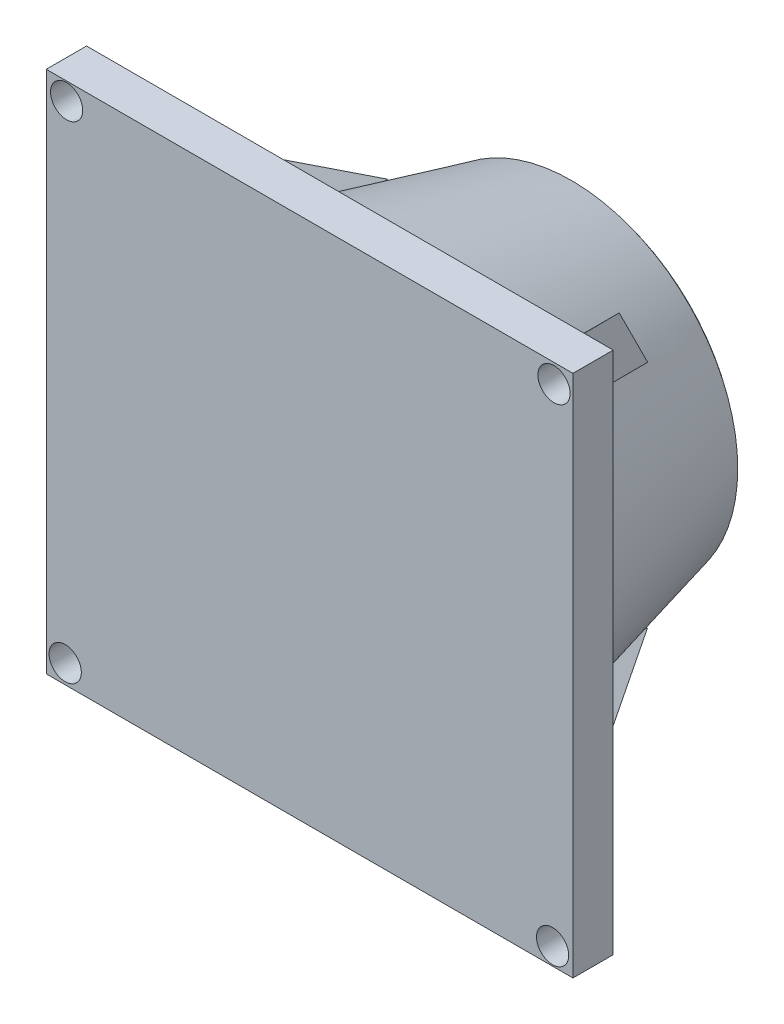
SolidWorks part; units mm, degrees
ref_plane "Piano frontale" through (0, 0, 0) normal (0, 0, 1) x (1, 0, 0)
ref_plane "Piano superiore" through (0, 0, 0) normal (0, 1, 0) x (1, 0, 0)
ref_plane "Piano destro" through (0, 0, 0) normal (1, 0, 0) x (0, 0, -1)
ref_plane "Piano5" through (0, 0, 10) normal (0, 0, 1) x (1, 0, 0)
sketch "Schizzo1" plane through (0, 0, 10) normal (0, 0, 1) x (1, 0, 0)
  arc A3 (159.4619, 183.1285) -> (159.4619, 201.9529) centre (159.4619, 192.5407) ccw
  arc A4 (159.4619, 201.9529) -> (159.4619, 183.1285) centre (159.4619, 192.5407) ccw
  arc A5 (142.3549, 173.8547) -> (142.3549, 155.0303) centre (142.3549, 164.4425) ccw
  arc A6 (142.3549, 155.0303) -> (142.3549, 173.8547) centre (142.3549, 164.4425) ccw
  arc A7 (142.3549, -155.0303) -> (142.3549, -173.8547) centre (142.3549, -164.4425) ccw
  arc A8 (142.3549, -173.8547) -> (142.3549, -155.0303) centre (142.3549, -164.4425) ccw
  arc A9 (159.4619, -183.1285) -> (159.4619, -201.9529) centre (159.4619, -192.5407) ccw
  arc A10 (159.4619, -201.9529) -> (159.4619, -183.1285) centre (159.4619, -192.5407) ccw
  arc A11 (-217.5, 9.4122) -> (-217.5, -9.4122) centre (-217.5, 0) ccw
  arc A12 (-217.5, -9.4122) -> (-217.5, 9.4122) centre (-217.5, 0) ccw
  arc A13 (-250, 9.4122) -> (-250, -9.4122) centre (-250, 0) ccw
  arc A14 (-250, -9.4122) -> (-250, 9.4122) centre (-250, 0) ccw
  circle A15 centre (0, 0) radius 400
  dimension "D1" = 800
  dimension "D2" = 0
  dimension "D3" = 217.5
  dimension "D4" = 250
  dimension "D5" = 217.5
  dimension "D6" = 250
  dimension "D7" = 217.5
  dimension "D8" = 250
extrude "Estrusione-Estrusione2" add sketch "Schizzo1" against normal blind 10
ref_plane "Piano1" through (0, 0, 560) normal (0, 0, 1) x (1, 0, 0)
sketch "Schizzo2" plane through (0, 0, 560) normal (0, 0, 1) x (1, 0, 0)
  circle A2 centre (0, 0) radius 550
  dimension "D1" = 1100
  dimension "D2" = 0
extrude "Estrusione-Estrusione3" add sketch "Schizzo2" against normal up to surface (550 mm away) draft 14 contours A2
sketch "Schizzo7" plane through (0, 0, 560) normal (0, 0, 1) x (1, 0, 0)
  line L1 (-653.7561, 650) -> (653.7561, 650)
  line L2 (-653.7561, 650) -> (-653.7561, -650)
  line L3 (-653.7561, -650) -> (653.7561, -650)
  line L4 (653.7561, 650) -> (653.7561, -650)
  line L5 (-653.7561, 650) -> (653.7561, -650) construction
  line L6 (-653.7561, -650) -> (653.7561, 650) construction
  circle A0 centre (0, 0) radius 550 construction
  circle A1 centre (0, 0) radius 550
  dimension "D1" = 1300
extrude "Estrusione-Estrusione4" add sketch "Schizzo7" along normal blind 100 separate body
ref_plane "Piano3" through (0, 0, 0) normal (0.7051, -0.7091, 0) x (-0.7091, -0.7051, 0)
sketch "Schizzo15" plane through (0, 0, 0) normal (0.7051, -0.7091, 0) x (-0.7091, -0.7051, 0)
  line L0 (-721.8986, -560) -> (-454.9433, -178.7483)
  line L1 (-5.3119, -560) -> (-921.8986, -560) construction
  line L2 (-412.8696, -10) -> (-550, -560) construction
  line L3 (-454.9433, -178.7483) -> (-454.9433, -560)
  line L4 (-454.9433, -560) -> (-721.8986, -560)
  dimension "D1" = 55
  dimension "D2" = 200
extrude "Estrusione-Estrusione15" add sketch "Schizzo15" along direction (0.7051, -0.7091, 0) on the side of the normal mid plane 100 separate body
sketch "Schizzo16" plane through (0, 0, 560) normal (0, 0, -1) x (-1, 0, 0)
  line L0 (-207.3477, 206.1564) -> (207.3477, -206.1564) construction
  circle A0 centre (-606.7222, 603.2363) radius 40
  dimension "D1" = 80
extrude "Taglio-Estrusione1" cut sketch "Schizzo16" against normal blind 183
sketch "Schizzo17" plane through (0, 0, 0) normal (0.7051, -0.7091, 0) x (-0.7091, -0.7051, 0)
  line L0 (721.8986, -560) -> (454.9433, -178.7483)
  line L1 (921.8986, -560) -> (-5.3119, -560) construction
  line L2 (550, -560) -> (412.8696, -10) construction
  line L3 (721.8986, -560) -> (454.9433, -560)
  line L4 (454.9433, -560) -> (454.9433, -178.7483)
  dimension "D1" = 200
  dimension "D2" = 55
extrude "Estrusione-Estrusione21" add sketch "Schizzo17" along direction (0.7051, -0.7091, 0) on the side of the normal mid plane 100 separate body
ref_plane "Piano4" through (0, 0, 0) normal (0.7051, 0.7091, 0) x (0.7091, -0.7051, 0)
sketch "Schizzo18" plane through (0, 0, 0) normal (0.7051, 0.7091, 0) x (0.7091, -0.7051, 0)
  line L0 (-721.8986, -560) -> (-454.9433, -178.7483)
  line L1 (5.3119, -560) -> (-921.8986, -560) construction
  line L2 (-412.8696, -10) -> (-550, -560) construction
  line L3 (-454.9433, -178.7483) -> (-454.9433, -560)
  line L4 (-454.9433, -560) -> (-721.8986, -560)
  line L5 (721.8986, -560) -> (454.9433, -178.7483)
  line L6 (921.8986, -560) -> (5.3119, -560) construction
  line L7 (550, -560) -> (412.8696, -10) construction
  line L8 (454.9433, -178.7483) -> (454.9433, -560)
  line L9 (454.9433, -560) -> (721.8986, -560)
  dimension "D1" = 200
  dimension "D2" = 55
  dimension "D3" = 200
  dimension "D4" = 55
extrude "Estrusione-Estrusione23" add sketch "Schizzo18" along normal mid plane 100 separate body
pattern_circular "RipetizioneCircolare3" count 4 over 360 about axis through (0, 0, 0) along (0, 0, 1) of "Taglio-Estrusione1"
sketch "Schizzo19" plane through (0, 0, 560) normal (0, 0, 1) x (1, 0, 0)
  circle A0 centre (0, 0) radius 550 construction
  circle A1 centre (0, 0) radius 550
extrude "Estrusione-Estrusione24" add sketch "Schizzo19" along normal up to surface (100 mm away) up to face at (-563.2363, 606.7222, 660)
fillet "Raccordo1" radius 13 1 edges at (400, 0, 10)
